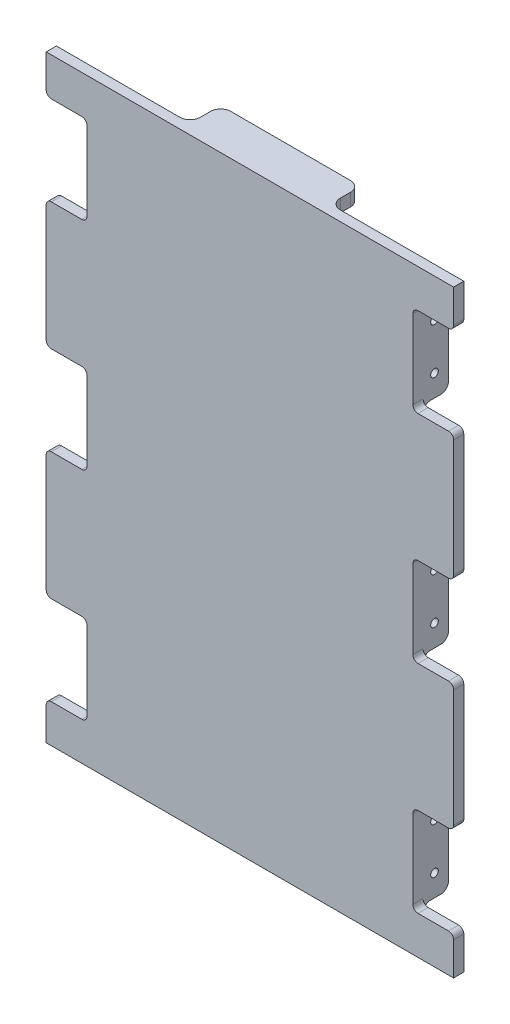
SolidWorks part; units mm, degrees
ref_plane "Front Plane" through (0, 0, 0) normal (0, 0, 1) x (1, 0, 0)
ref_plane "Top Plane" through (0, 0, 0) normal (0, 1, 0) x (1, 0, 0)
ref_plane "Right Plane" through (0, 0, 0) normal (1, 0, 0) x (0, 0, -1)
sketch "Sketch1" plane through (0, 0, 0) normal (0, 0, 1) x (1, 0, 0)
  line L0 (-64.0501, 42.5) -> (64, 42.5) construction
  line L5 (80, 25) -> (80, -25)
  line L8 (80, 25) -> (64, 25)
  line L9 (64, 60) -> (64, 25)
  line L10 (80, -60) -> (80, -75)
  line L11 (80, -60) -> (64, -60)
  line L13 (80, -25) -> (64, -25)
  line L14 (64, -60) -> (64, -25)
  line L15 (0, 75) -> (0, -75) construction
  line L25 (-64, -60) -> (-64, -25)
  line L26 (-80, -25) -> (-64, -25)
  line L27 (-80, -60) -> (-64, -60)
  line L28 (-80, -60) -> (-80, -75)
  line L29 (-64, 60) -> (-64, 25)
  line L30 (-80, 25) -> (-64, 25)
  line L32 (-80, 25) -> (-80, -25)
  line L35 (-80, -75) -> (80, -75)
  line L36 (0, 10) -> (0, 160) construction
  line L37 (-80, 160) -> (80, 160)
  line L38 (-80, 60) -> (-80, 110)
  line L39 (-80, 60) -> (-64, 60)
  line L40 (-80, 145) -> (-80, 160)
  line L41 (-80, 145) -> (-64, 145)
  line L42 (-80, 110) -> (-64, 110)
  line L43 (-64, 145) -> (-64, 110)
  line L44 (64, 145) -> (64, 110)
  line L45 (80, 110) -> (64, 110)
  line L46 (80, 145) -> (64, 145)
  line L47 (80, 145) -> (80, 160)
  line L48 (80, 60) -> (64, 60)
  line L49 (80, 60) -> (80, 110)
  point P27 (-64, 42.5)
extrude "Boss-Extrude1" add sketch "Sketch1" against normal blind 4
sketch "Sketch4" plane through (0, 0, 0) normal (0, 0, 1) x (1, 0, 0)
  line L0 (-64, -60) -> (-54, -60)
  line L5 (80, 0) -> (-80, 0) construction
  line L6 (64, 60) -> (54, 60)
  line L7 (64, 60) -> (64, 25)
  line L8 (64, 25) -> (54, 25)
  line L9 (54, 60) -> (54, 25)
  line L10 (80, -25) -> (80, 25) construction
  line L11 (-80, 25) -> (-80, -25) construction
  line L12 (54, -60) -> (54, -25)
  line L13 (64, -25) -> (54, -25)
  line L14 (64, -60) -> (64, -25)
  line L15 (64, -60) -> (54, -60)
  line L16 (0, 75) -> (0, -75) construction
  line L18 (-80, -75) -> (80, -75) construction
  line L19 (-64, -60) -> (-64, -25)
  line L20 (-64, -25) -> (-54, -25)
  line L21 (-54, -60) -> (-54, -25)
  line L22 (-54, 60) -> (-54, 25)
  line L23 (-64, 25) -> (-54, 25)
  line L24 (-64, 60) -> (-64, 25)
  line L25 (-64, 60) -> (-54, 60)
  line L26 (-80, 85) -> (80, 85) construction
  line L27 (-80, 110) -> (-80, 60) construction
  line L28 (80, 60) -> (80, 110) construction
  line L29 (-64, 110) -> (-54, 110)
  line L30 (-64, 110) -> (-64, 145)
  line L31 (-64, 145) -> (-54, 145)
  line L32 (-54, 110) -> (-54, 145)
  line L33 (54, 110) -> (54, 145)
  line L34 (64, 145) -> (54, 145)
  line L35 (64, 110) -> (64, 145)
  line L36 (64, 110) -> (54, 110)
extrude "Boss-Extrude3" add sketch "Sketch4" against normal blind 14
sketch "Sketch6" plane through (64, 0, 0) normal (1, 0, 0) x (0, 0, -1)
  line L0 (8.5, -60) -> (8.5, -25) construction
  line L1 (14, 110) -> (14, 145) construction
  line L2 (0, 60) -> (0, 110) construction
  line L3 (8.5, -42.5) -> (14, -42.5) construction
  line L4 (0, -25) -> (0, 25) construction
  line L5 (8.5, 0) -> (0, 0) construction
  line L7 (8.5, 42.5) -> (14, 42.5) construction
  line L8 (8.5, 60) -> (8.5, 25) construction
  line L9 (8.5, 85) -> (0, 85) construction
  line L11 (8.5, 110) -> (8.5, 145) construction
  line L12 (8.5, 127.5) -> (14, 127.5) construction
  line L13 (8.5, 145) -> (8.5, -60) construction
  line L16 (8.5, 42.5) -> (14, 42.5) construction
  circle A0 centre (8.5, -51.5) radius 1.5
  circle A1 centre (8.5, -33.5) radius 1.5
  circle A2 centre (8.5, 33.5) radius 1.5
  circle A3 centre (8.5, 51.5) radius 1.5
  circle A4 centre (8.5, 118.5) radius 1.5
  circle A5 centre (8.5, 136.5) radius 1.5
  point P4 (0, 0)
  point P5 (14, 127.5)
  point P14 (0, 0)
  point P17 (0, 85)
extrude "Cut-Extrude1" cut sketch "Sketch6" against normal up to surface (128 mm away) up to face at (-64, -42.5, -6)
fillet "Fillet2" radius 3 24 edges at (-59, -25, -14) (-59, -60, -14) (-59, 60, -14) (-59, 25, -14) (-59, 145, -14) (-59, 110, -14) (59, 145, -14) (59, 110, -14) (59, 25, -14) (59, 60, -14) (59, -25, -14) (59, -60, -14) (59, 145, -4) (59, 110, -4) (59, 60, -4) (59, 25, -4) (59, -25, -4) (59, -60, -4) (-59, -25, -4) (-59, -60, -4) (-59, 25, -4) (-59, 60, -4) (-59, 110, -4) (-59, 145, -4)
fillet "Fillet3" radius 2 24 edges at (80, -60, -2) (64, -60, -2) (80, -25, -2) (64, -25, -2) (80, 25, -2) (64, 25, -2) (64, 60, -2) (80, 60, -2) (80, 110, -2) (64, 110, -2) (64, 145, -2) (80, 145, -2) (-80, 145, -2) (-64, 145, -2) (-64, 110, -2) (-80, 110, -2) (-80, 60, -2) (-64, 60, -2) (-64, 25, -2) (-80, 25, -2) (-80, -25, -2) (-64, -25, -2) (-80, -60, -2) (-64, -60, -2)
sketch "Sketch7" plane through (0, 0, -4) normal (0, 0, -1) x (-1, 0, 0)
  line L0 (2.5, 125.5) -> (32.5, 125.5)
  line L8 (32.5, 40.5) -> (2.5, 40.5)
  line L9 (32.5, -40.5) -> (32.5, 40.5)
  line L10 (2.5, -40.5) -> (32.5, -40.5)
  line L11 (2.5, 40.5) -> (2.5, -40.5)
  line L13 (36.5, 125.5) -> (64, 125.5)
  line L16 (2.5, 44.5) -> (32.5, 44.5)
  line L17 (32.5, 44.5) -> (32.5, 125.5)
  line L19 (2.5, 125.5) -> (2.5, 44.5)
  line L24 (-32.5, -40.5) -> (-2.5, -40.5)
  line L25 (-32.5, 40.5) -> (-32.5, -40.5)
  line L26 (-2.5, 40.5) -> (-32.5, 40.5)
  line L27 (-2.5, -40.5) -> (-2.5, 40.5)
  line L32 (-2.5, 125.5) -> (-32.5, 125.5)
  line L33 (-32.5, 125.5) -> (-32.5, 44.5)
  line L34 (-32.5, 44.5) -> (-2.5, 44.5)
  line L35 (-2.5, 44.5) -> (-2.5, 125.5)
  line L76 (0, 129.5) -> (-64, 129.5)
  line L77 (-64, 129.5) -> (-64, 125.5)
  line L78 (-64, 125.5) -> (-36.5, 125.5)
  line L79 (-36.5, 125.5) -> (-36.5, 44.5)
  line L80 (-36.5, 44.5) -> (-64, 44.5)
  line L81 (-64, 44.5) -> (-64, 40.5)
  line L82 (-64, 40.5) -> (-36.5, 40.5)
  line L83 (-36.5, 40.5) -> (-36.5, -40.5)
  line L84 (-36.5, -40.5) -> (-64, -40.5)
  line L85 (-64, -40.5) -> (-64, -44.5)
  line L86 (-64, -44.5) -> (0, -44.5)
  line L87 (0, -44.5) -> (64, -44.5)
  line L88 (64, -44.5) -> (64, -40.5)
  line L89 (64, -40.5) -> (36.5, -40.5)
  line L90 (36.5, -40.5) -> (36.5, 40.5)
  line L91 (36.5, 40.5) -> (64, 40.5)
  line L92 (64, 40.5) -> (64, 44.5)
  line L93 (64, 44.5) -> (36.5, 44.5)
  line L94 (36.5, 44.5) -> (36.5, 125.5)
  line L96 (64, 125.5) -> (64, 129.5)
  line L97 (64, 129.5) -> (0, 129.5)
  dimension "D1" = 4
  dimension "D2" = 4
  dimension "D3" = 4
  dimension "D4" = 4
  dimension "D5" = 30
  dimension "D6" = 30
  dimension "D7" = 30
  dimension "D8" = 30
extrude "Boss-Extrude4" add sketch "Sketch7" along normal blind 7
fillet "Fillet4" radius 4 36 edges at (54, -44.5, -7.5) (54, -40.5, -7.5) (36.5, -40.5, -7.5) (32.5, -40.5, -7.5) (-2.5, -40.5, -7.5) (2.5, -40.5, -7.5) (-32.5, -40.5, -7.5) (-36.5, -40.5, -7.5) (-54, -44.5, -7.5) (-54, -40.5, -7.5) (-54, 40.5, -7.5) (-54, 44.5, -7.5) (-36.5, 44.5, -7.5) (-36.5, 40.5, -7.5) (-32.5, 40.5, -7.5) (-32.5, 44.5, -7.5) (54, 40.5, -7.5) (54, 44.5, -7.5) (-2.5, 44.5, -7.5) (-2.5, 40.5, -7.5) (2.5, 40.5, -7.5) (2.5, 44.5, -7.5) (36.5, 44.5, -7.5) (36.5, 40.5, -7.5) (32.5, 40.5, -7.5) (32.5, 44.5, -7.5) (54, 129.5, -7.5) (54, 125.5, -7.5) (36.5, 125.5, -7.5) (32.5, 125.5, -7.5) (2.5, 125.5, -7.5) (-2.5, 125.5, -7.5) (-32.5, 125.5, -7.5) (-36.5, 125.5, -7.5) (-54, 125.5, -7.5) (-54, 129.5, -7.5)
sketch "Sketch8" plane through (0, 0, -4) normal (0, 0, -1) x (-1, 0, 0)
  line L0 (-80, 160) -> (80, 160) construction
  line L1 (27.5, 160) -> (-27.5, 160)
  line L2 (27.5, 160) -> (27.5, 155)
  line L3 (27.5, 155) -> (-27.5, 155)
  line L4 (-27.5, 160) -> (-27.5, 155)
extrude "Boss-Extrude5" add sketch "Sketch8" along normal blind 12
fillet "Fillet5" radius 4 4 edges at (-27.5, 157.5, -4) (-27.5, 157.5, -16) (27.5, 157.5, -16) (27.5, 157.5, -4)
